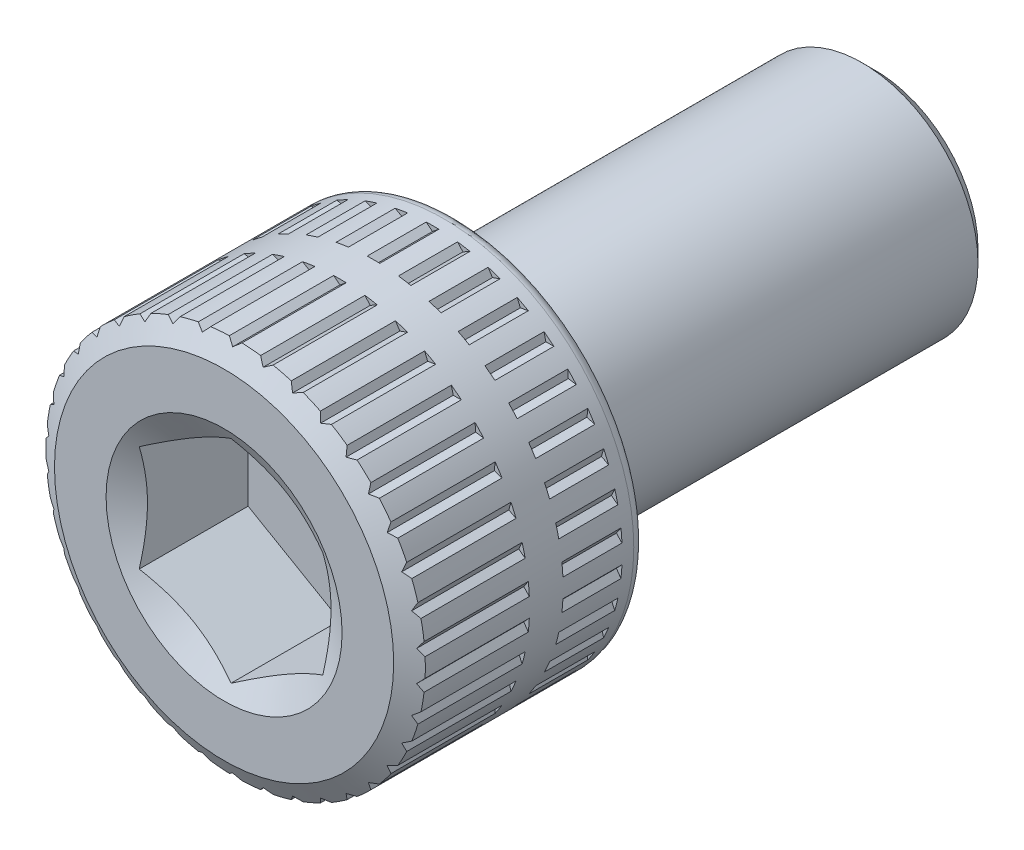
SolidWorks part; units mm, degrees
material "6061-T6 (SS)"
ref_plane "Front Plane" through (0, 0, 0) normal (0, 0, 1) x (1, 0, 0)
ref_plane "Top Plane" through (0, 0, 0) normal (0, 1, 0) x (1, 0, 0)
ref_plane "Right Plane" through (0, 0, 0) normal (1, 0, 0) x (0, 0, -1)
sketch "Sketch1" plane through (0, 0, 0) normal (1, 0, 0) x (0, 0, -1)
  line L0 (4.9276, 0) -> (-4.9276, 0) construction
  line L1 (-1.4224, 2.8702) -> (-1.4224, -2.8702) construction
  line L2 (4.9276, 1.7526) -> (4.9276, -1.7526) construction
  line L3 (4.878, 1.8385) -> (5.2749, 1.1511) construction
  line L4 (5.2253, 1.237) -> (5.3245, 1.237) construction
  line L5 (5.2749, 1.1511) -> (5.6717, 1.8385) construction
  line L6 (5.6717, 1.8385) -> (4.878, 1.8385) construction
  line L7 (5.2749, 1.237) -> (5.2749, 1.1511) construction
  line L8 (5.2749, 1.8385) -> (5.2749, 1.7526) construction
  line L9 (5.6221, 1.7526) -> (4.9276, 1.7526) construction
  point P4 (-1.4224, 0)
  point P6 (-1.4224, 1.3891)
  point P7 (2.1495, -1.7526)
  point P20 (5.2749, 1.7956)
sketch "Sketch2" plane through (0, 0, 0) normal (1, 0, 0) x (0, 0, -1)
  line L0 (4.9276, 0) -> (4.9276, 1.5542)
  line L1 (4.9276, 1.7526) -> (4.9276, -1.7526) construction
  line L2 (4.9276, 1.5542) -> (4.7292, 1.7526)
  line L3 (4.7292, 1.7526) -> (-1.4224, 1.7526)
  line L4 (-1.4224, 1.7526) -> (-1.4224, 2.6949)
  line L5 (-1.5977, 2.8702) -> (-4.7523, 2.8702)
  line L6 (-4.9276, 2.6949) -> (-4.9276, 0)
  line L7 (4.9276, 0) -> (-4.9276, 0) construction
  line L8 (-4.9276, 0) -> (4.9276, 0)
  arc A0 (-1.4224, 2.6949) -> (-1.5977, 2.8702) centre (-1.5977, 2.6949) ccw
  arc A1 (-4.7523, 2.8702) -> (-4.9276, 2.6949) centre (-4.7523, 2.6949) ccw
  point P19 (-1.4224, 2.8702)
  dimension "D1" = 0.1984
  dimension "D2" = 45
revolve "Revolve1" add sketch "Sketch2" angle 360 about L0
sketch "Sketch3" plane through (0, 0, 0) normal (0, 0, 1) x (1, 0, 0)
  line L1 (-1.3891, 0.802) -> (-1.3891, -0.802)
  line L2 (-1.3891, -0.802) -> (0, -1.604)
  line L3 (0, -1.604) -> (1.3891, -0.802)
  line L4 (1.3891, -0.802) -> (1.3891, 0.802)
  line L5 (1.3891, 0.802) -> (0, 1.604)
  line L6 (0, 1.604) -> (-1.3891, 0.802)
  circle A0 centre (0, 0) radius 1.3891 construction
  circle A1 centre (0, 0) radius 2.8702 construction
extrude "Cut-Extrude1" cut sketch "Sketch3" against normal blind 1.7526 from vertex starting at point (0, 0, 4.9276)
sketch "Sketch4" plane through (0, 0, 4.9276) normal (0, 0, 1) x (1, 0, 0)
  line L0 (0, 1.604) -> (0, 1.9676) construction
  line L1 (0, 1.9676) -> (0, 2.3313) construction
  line L2 (0, 2.3313) -> (0, 2.6949) construction
  circle A0 centre (0, 0) radius 1.7858
  point P12 (0, 1.7858)
extrude "Cut-Extrude2" cut sketch "Sketch4" against normal through all draft 60
split "Split1" [suppressed] bodies to split 106 112
sketch "Sketch5" [suppressed] plane through (0, 0, 0) normal (1, 0, 0) x (0, 0, -1)
  line L0 (5.2253, 1.237) -> (5.3245, 1.237)
  line L1 (5.3245, 1.237) -> (5.6469, 1.7956)
  line L2 (5.6469, 1.7956) -> (4.9028, 1.7956)
  line L3 (4.9028, 1.7956) -> (5.2253, 1.237)
  line L4 (4.878, 1.8385) -> (5.2749, 1.1511) construction
sketch "Sketch6" [suppressed] plane through (0, 0, -4.9276) normal (0, 0, -1) x (-1, 0, 0)
  circle A0 centre (0, 0) radius 1.7526
curve "Helix/Spiral1" [suppressed] pitch 0.7937 height 7.1437 turns 9
sweep "Cut-Sweep1" [suppressed] cut profiles "Sketch5" path "Helix/Spiral1"
sketch "Sketch7" [suppressed] plane through (0, 0, 1.4224) normal (0, 0, -1) x (-1, 0, 0)
  circle A0 centre (0, 0) radius 1.8034
  circle A1 centre (0, 0) radius 1.7526 construction
  dimension "D1" = 0.0508
extrude "Boss-Extrude1" [suppressed] add sketch "Sketch7" along normal through all draft 20 and the other way blind 0.3505
ref_plane "Plane1" through (0, 0, 1.7729) normal (0, 0, -1) x (-1, 0, 0)
other "DeleteFace1" face at (-2.6949, 0, 4.9276) and patch yes
chamfer "Chamfer1" distance 0.1753 angle 60 1 edges at (2.8702, 0, 4.9276) first distance on face at (2.8702, 0, 4.9276)
sketch "Sketch8" plane through (0, 0, 1.7729) normal (0, 0, -1) x (-1, 0, 0)
  line L0 (0.0953, 2.8686) -> (0, 0) construction
  line L1 (0, 0) -> (-0.0952, 2.8686) construction
  line L7 (-0.0952, 2.8686) -> (0, 2.7924)
  line L8 (0, 2.7924) -> (0.0953, 2.8686)
  arc A1 (0.0953, 2.8686) -> (-0.0952, 2.8686) centre (0, 0) ccw
  circle A2 centre (0, 0) radius 2.8702 construction
  point P2 (0, 2.8702)
  dimension "D3" = 0.0762
  dimension "D1" = 0.1905
extrude "Cut-Extrude3" cut sketch "Sketch8" against normal blind 0.8938
extrude "Cut-Extrude4" cut sketch "Sketch8<4>" against normal through all from offset 1.4021 offset against normal yes
sketch "Sketch8<4>" plane through (0, 0, 1.7729) normal (0, 0, -1) x (-1, 0, 0) same geometry as "Sketch8"
pattern_circular "CirPattern1" count 38 over 360 about axis through (0, 0, -4.9276) along (0, 0, 1) of "Cut-Extrude3", "Cut-Extrude4" reverse direction yes
equation "\"Pitch/8@Sketch1\" = \"Pitch@Sketch1\" / 8"
equation "\"Thread Note@Sketch1\" = \"Pitch@Sketch1\" * 3.5"
equation "\"D1@Sketch2\"=\"Pitch@Sketch1\"*.25"
equation "\"D3@Sketch2\"=\"Head Height@Sketch1\"*.05"
equation "\"D1@Cut-Extrude1\" = \"Head Height@Sketch1\" * .5"
equation "\"D3@Helix/Spiral1\" = \"Length@Sketch1\" + \"Pitch@Sketch1\""
equation "\"D4@Helix/Spiral1\" = \"Pitch@Sketch1\""
equation "\"D2@Boss-Extrude1\" = \"Head Height@Sketch1\" * .1"
equation "\"D1\"= \"Screw Size Decimal Equivalent@Sketch1\" * .4"
equation "\"D1@Plane1\" = \"D3@Sketch2\" * 2"
equation "\"D1@Cut-Extrude3\"=( \"Head Height@Sketch1\" - \"D1@Plane1\" - \"D3@Sketch2\" )  * .3"
equation "\"D1@CirPattern1\" =  ( \"Head Diameter@Sketch1\" * pi )  /  ( 2.5 * \"D1@Sketch8\" ) "
equation "\"D1@Chamfer1\" = \"D3@Sketch2\""
equation "\"D19@Cut-Extrude4\" =  ( \"Head Height@Sketch1\" * .5 )  - \"D1@Plane1\""
